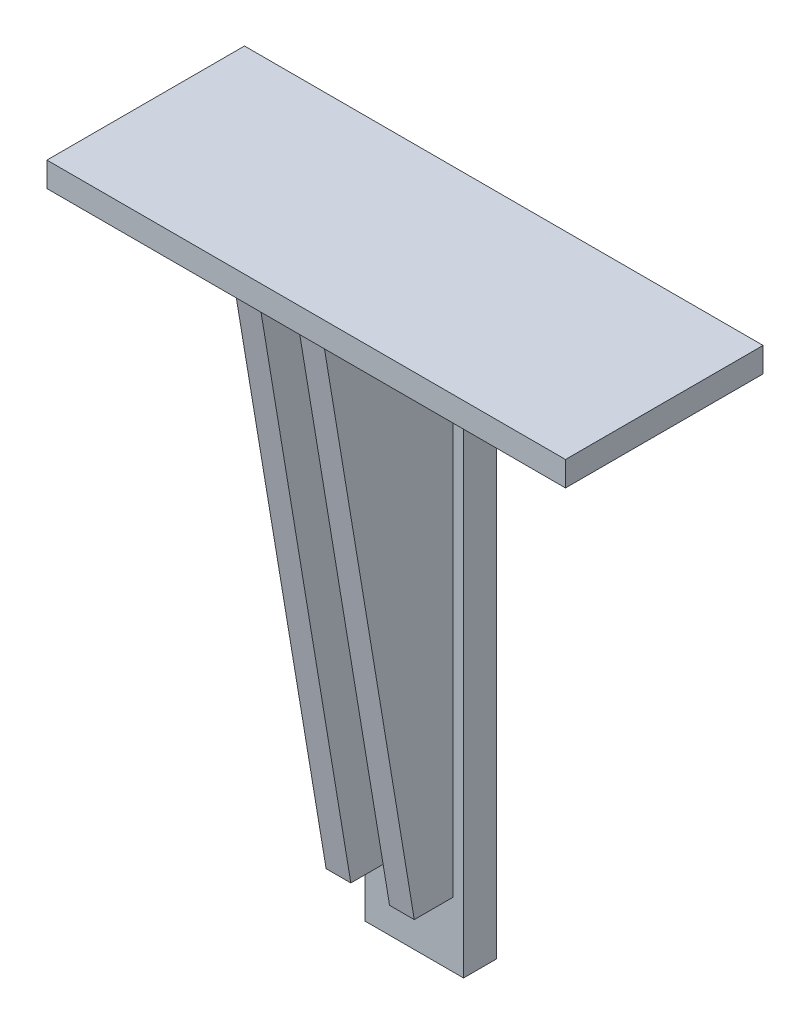
SolidWorks part; units mm, degrees
ref_plane "Front Plane" through (0, 0, 0) normal (0, 0, 1) x (1, 0, 0)
ref_plane "Top Plane" through (0, 0, 0) normal (0, 1, 0) x (1, 0, 0)
ref_plane "Right Plane" through (0, 0, 0) normal (1, 0, 0) x (0, 0, -1)
sketch "Sketch1" plane through (0, 0, 0) normal (1, 0, 0) x (0, 0, -1)
  line L0 (-66.675, 0) -> (9.525, 0)
  line L2 (0, 0) -> (9.525, 0)
  line L4 (9.525, 9.525) -> (-66.675, 9.525)
  line L5 (-66.675, 9.525) -> (-66.675, 0)
  line L7 (0, 0) -> (9.525, 0)
  line L8 (0, 0) -> (0, -250)
  line L9 (0, -250) -> (9.525, -250)
  line L10 (9.525, 0) -> (9.525, -250)
  line L16 (9.525, 9.525) -> (9.525, 0)
  line L19 (-66.675, 0) -> (-66.675, -3.175)
  line L20 (-66.675, -3.175) -> (9.525, -3.175)
  point P1 (0, 0)
  point P13 (9.525, -3.175)
  dimension "D1" = 9.525
  dimension "D2" = 9.525
  dimension "D3" = 76.2
  dimension "D5" = 250
  dimension "D7" = 12.7
extrude "Boss-Extrude5" add sketch "Sketch1" along normal blind 125 and the other way blind 75 contours L16 L4 L5 L0 region at (0, 4.7625, 28.575)
extrude "Boss-Extrude6" add sketch "Sketch1<5>" along normal mid plane 38 separate body contours L10 L0 L8 L9 | L8 L20 L10 L0 region at (0, -1.5875, -4.7625) region at (0, -126.5875, -4.7625)
sketch "Sketch1<5>" plane through (0, 0, 0) normal (1, 0, 0) x (0, 0, -1) same geometry as "Sketch1"
sketch "Sketch2" plane through (0, 0, -9.525) normal (0, 0, -1) x (-1, 0, 0)
  line L0 (0, 0) -> (0, -263.8174) construction
  line L1 (-19, 0) -> (-15, 0)
  line L2 (-15, -4.5282) -> (15, -4.5282)
  line L3 (-15, -4.5282) -> (-15, -36.0894)
  line L4 (-15, -36.0894) -> (15, -36.0894)
  line L5 (15, -4.5282) -> (15, -36.0894)
  line L6 (-19, 0) -> (19, 0) construction
  line L7 (-15, 0) -> (-15, -250)
  line L8 (-19, -250) -> (19, -250) construction
  line L9 (-15, -250) -> (-19, -250)
  line L10 (-19, -250) -> (-19, 0)
  line M8 (19, 0) -> (-19, 0)
  line M9 (-19, 0) -> (-19, -250)
  line M10 (-19, -250) -> (19, -250)
  dimension "D1" = 30
  dimension "D2" = 4
extrude "Boss-Extrude7" add sketch "Sketch2" along normal blind 3.175 contours L7 L3 M8 M9 M10 region at (17, -125, -9.525)
sketch "Sketch6" plane through (0, 0, 0) normal (0, -1, 0) x (1, 0, 0)
  line L0 (19, 0) -> (-19, 0) construction
  line L1 (-10, 5) -> (10, 5)
  line L2 (-10, 5) -> (-10, 0)
  line L3 (-10, 0) -> (10, 0)
  line L4 (10, 5) -> (10, 0)
  line L5 (0, 0) -> (0, 18.4937) construction
  line L6 (0, -9.525) -> (0, 66.675) construction
  line L7 (19, 0) -> (19, -12.7) construction
  line L8 (19, -2.525) -> (24, -2.525)
  line L9 (19, -2.525) -> (19, -7.525)
  line L10 (19, -7.525) -> (24, -7.525)
  line L11 (24, -2.525) -> (24, -7.525)
  line L12 (-75, -9.525) -> (125, -9.525) construction
  dimension "D1" = 5
  dimension "D2" = 20
  dimension "D3" = 2
  dimension "D4" = 5
  dimension "D5" = 5
extrude "Boss-Extrude8" add sketch "Sketch6" along normal up to vertex (3.175 mm away) up to point (0, -3.175, 66.675)
sketch "Sketch3" plane through (0, 0, 0) normal (0, 1, 0) x (1, 0, 0)
  line L0 (0, 0) -> (0, 9.525) construction
  line L1 (-19, 4.7625) -> (19, 4.7625) construction
  line L2 (-19, 0) -> (-19, 9.525) construction
  line L3 (19, 0) -> (19, 12.7) construction
  line L4 (0, 8.8001) -> (0, 1.2807) construction
  circle A0 centre (-14, 4.7625) radius 2
  circle A1 centre (0, 4.7625) radius 2
  circle A2 centre (14, 4.7625) radius 2
  dimension "D1" = 4
  dimension "D2" = 14
sketch "Sketch7" plane through (0, 0, -9.525) normal (0, 0, -1) x (-1, 0, 0)
  line L0 (-15, 0) -> (-15, -250) construction
  line L1 (-15, -10.1116) -> (-5.475, -10.1116)
  line L2 (-15, -10.1116) -> (-15, -28.0084)
  line L3 (-15, -28.0084) -> (-5.475, -28.0084)
  line L4 (-5.475, -10.1116) -> (-5.475, -28.0084)
  line L5 (9.475, -9.6486) -> (19, -9.6486)
  line L6 (9.475, -9.6486) -> (9.475, -28.9758)
  line L7 (9.475, -28.9758) -> (19, -28.9758)
  line L8 (19, -9.6486) -> (19, -28.9758)
  line L9 (19, 0) -> (19, -250) construction
  point P8 (7.9929, -9.6486)
  point P13 (0, 0)
  point P14 (0, 0)
  point P15 (0, 0)
  point P16 (0, 0)
  dimension "D1" = 9.525
sketch "Sketch5" plane through (0, 0, 0) normal (1, 0, 0) x (0, 0, -1)
  line L0 (-50.8, 0) -> (-50.8, -10)
  line L2 (-50.8, -10) -> (-15, -225)
  line L3 (-15, -225) -> (0, -225)
  line L4 (0, 0) -> (0, -250) construction
  line L5 (0, -225) -> (0, 0)
  line L6 (0, 0) -> (-50.8, 0)
  line L7 (0, -250) -> (9.525, -250) construction
  line L8 (-66.675, 0) -> (9.525, 0) construction
  line L9 (-15, 0) -> (-15, -8.65)
  line L10 (-8.65, -15) -> (0, -15)
  arc A0 (-15, -8.65) -> (-8.65, -15) centre (-8.65, -8.65) ccw
  point P18 (-15, -15)
  dimension "D8" = 6.35
  dimension "D1" = 50.8
  dimension "D2" = 15
  dimension "D3" = 25
  dimension "D4" = 10
  dimension "D5" = 225
  dimension "D6" = 15
  dimension "D7" = 15
extrude "Boss-Extrude9" add sketch "Sketch5" along normal up to vertex (15 mm away) from vertex separate body contours L10 L9 L6 L0 L2 L3 L5 region at (0, -94.2549, 18.8962) up to point (15, -28.0084, -9.525) starting at point (5.475, -28.0084, -9.525)
extrude "Boss-Extrude10" add sketch "Sketch5<3>" against normal up to vertex (19 mm away) from vertex separate body contours L10 L9 L6 L0 L2 L3 L5 region at (0, -94.2549, 18.8962) up to point (-19, -9.6486, -9.525) starting at point (-9.475, -9.6486, -9.525)
sketch "Sketch5<3>" plane through (0, 0, 0) normal (1, 0, 0) x (0, 0, -1) same geometry as "Sketch5"
